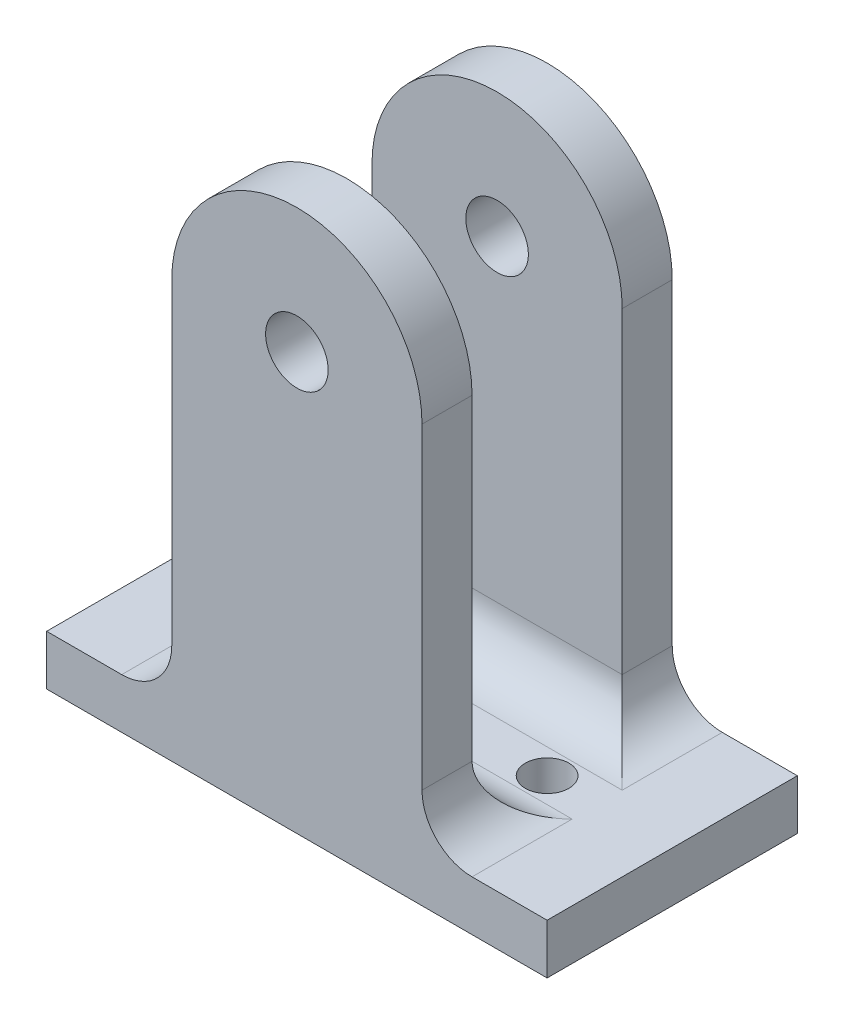
SolidWorks part; units mm, degrees
material "Custom Plastic"
ref_plane "Front Plane" through (0, 0, 0) normal (0, 0, 1) x (1, 0, 0)
ref_plane "Top Plane" through (0, 0, 0) normal (0, 1, 0) x (1, 0, 0)
ref_plane "Right Plane" through (0, 0, 0) normal (1, 0, 0) x (0, 0, -1)
sketch "Sketch1" plane through (0, 0, 0) normal (0, 1, 0) x (1, 0, 0)
  line L0 (0, 19.05) -> (76.2, 19.05) construction
  line L1 (0, 0) -> (76.2, 0)
  line L2 (0, 0) -> (0, 38.1)
  line L3 (0, 38.1) -> (76.2, 38.1)
  line L4 (76.2, 0) -> (76.2, 38.1)
  line L5 (38.1, 38.1) -> (38.1, 0) construction
  circle A0 centre (19.05, 19.05) radius 3.3274
  circle A1 centre (57.15, 19.05) radius 3.3274
  dimension "D3" = 6.6548
  dimension "D1" = 76.2
  dimension "D2" = 38.1
  dimension "D4" = 19.05
extrude "Boss-Extrude1" add sketch "Sketch1" along normal blind 7.62
ref_plane "Plane1" through (0, 0, -19.05) normal (0, 0, 1) x (1, 0, 0)
sketch "Sketch2" plane through (0, 0, 0) normal (0, 0, 1) x (1, 0, 0)
  line L3 (0, 0) -> (76.2, 0) construction
  line L5 (19.05, 0) -> (19.05, 63.5)
  line L7 (57.15, 0) -> (57.15, 63.5)
  line L8 (19.05, 0) -> (57.15, 0)
  line L9 (0, 7.62) -> (0, 0) construction
  arc A2 (19.05, 63.5) -> (57.15, 63.5) centre (38.1, 63.5) cw
  circle A3 centre (38.1, 63.5) radius 4.7625
  dimension "D2" = 19.05
  dimension "D3" = 19.05
  dimension "D4" = 9.525
  dimension "D1" = 63.5
extrude "Boss-Extrude2" add sketch "Sketch2" against normal blind 7.62
fillet "Fillet1" radius 7.62 3 edges at (38.1, 7.62, -7.62) (19.05, 7.62, -3.81) (57.15, 7.62, -3.81)
mirror "Mirror2" about plane through (0, 0, -19.05) normal (0, 0, 1) of "Boss-Extrude2", "Fillet1"
